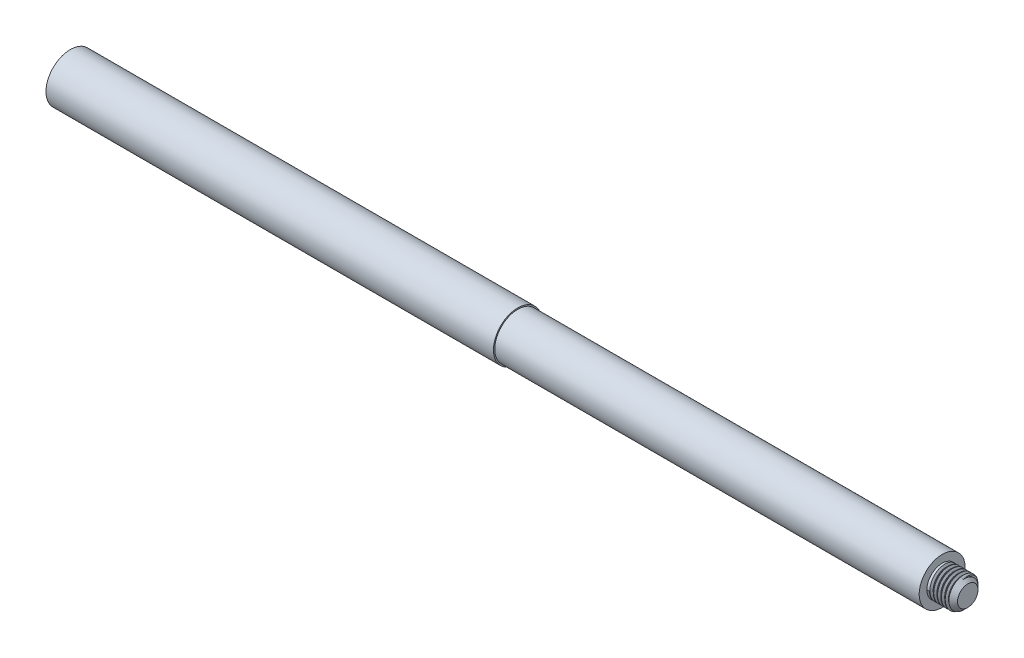
SolidWorks part; units mm, degrees
ref_plane "Płaszczyzna przednia" through (0, 0, 0) normal (0, 0, 1) x (1, 0, 0)
ref_plane "Płaszczyzna górna" through (0, 0, 0) normal (0, 1, 0) x (1, 0, 0)
ref_plane "Płaszczyzna prawa" through (0, 0, 0) normal (1, 0, 0) x (0, 0, -1)
sketch "Szkic1" plane through (0, 0, 0) normal (1, 0, 0) x (0, 0, -1)
  circle A0 centre (0, 0) radius 9
  dimension "D1" = 18
extrude "Dodanie-wyciągnięcie1" add sketch "Szkic1" along normal blind 166
sketch "Szkic2" plane through (0, 0, 0) normal (-1, 0, 0) x (0, 0, 1)
  circle A0 centre (0, 0) radius 9.5
  dimension "D1" = 19
extrude "Dodanie-wyciągnięcie2" add sketch "Szkic2" along normal blind 175
sketch "Szkic3" plane through (166, 0, 0) normal (1, 0, 0) x (0, 0, -1)
  circle A0 centre (0, 0) radius 6
  dimension "D1" = 12
extrude "Dodanie-wyciągnięcie3" add sketch "Szkic3" along normal blind 10
sketch "Szkic10" plane through (0, 0, 0) normal (0, 0, 1) x (1, 0, 0)
  line L1 (-175, 0) -> (166, 0) construction
  line L2 (-175, 9.5) -> (-175, -9.5) construction
  line L3 (166, -6) -> (166, 6) construction
  line L4 (-4.5, 0) -> (-4.5, 14.6263) construction
chamfer "Sfazowanie1" distance 2 angle 45 1 edges at (176, 0, -6)
thread "Gwint2" pitch 1.5 method cut profile "Profil gwintu2" start angle 0, offset 5, length 12, pitch 1.5, diameter 12
ref_plane "Płaszczyzna2" through (179, 0, 6) normal (0, -1, 0) x (0, 0, 1)
sketch "Profil gwintu2" plane through (179, 0, 6) normal (0, -1, 0) x (0, 0, 1)
  line L0 (0, 0) -> (0, 1.5) construction
  line L11 (0, 0) -> (0, 1.3125)
  line L12 (0, 1.3125) -> (-0.8119, 0.8437)
  line L13 (-0.8119, 0.8437) -> (-0.8119, 0.4687)
  line L15 (-0.8119, 0.4687) -> (0, 0)
  line L17 (-0.8119, 0.6562) -> (0, 0.6562) construction
  point P2 (0, 0)
  dimension "Pitch" = 1.5
  dimension "Profile_Angle" = 60
  dimension "Profile_Land" = 0.375
  dimension "Profile_Height" = 0.8119
